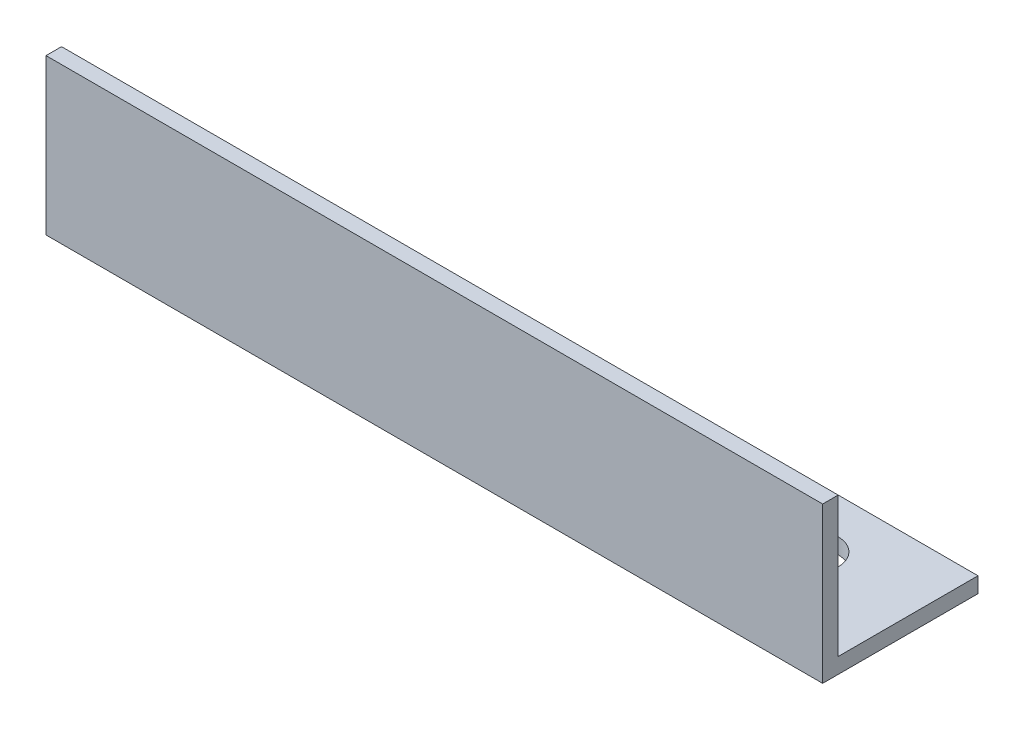
SolidWorks part; units mm, degrees
ref_plane "Спереди" through (0, 0, 0) normal (0, 0, 1) x (1, 0, 0)
ref_plane "Сверху" through (0, 0, 0) normal (0, 1, 0) x (1, 0, 0)
ref_plane "Справа" through (0, 0, 0) normal (1, 0, 0) x (0, 0, -1)
sketch "Эскиз1" plane through (0, 0, 0) normal (1, 0, 0) x (0, 0, -1)
  line L0 (0, 0) -> (0, 30)
  line L1 (0, 0) -> (30, 0)
extrude "Вытянуть-Тонкостенный1" add sketch "Эскиз1" along normal blind 150 thin thin type one direction reverse wall 3
sketch "Эскиз2" plane through (0, 0, 0) normal (0, -1, 0) x (1, 0, 0)
  line L0 (75, -35.357) -> (75, 2.5686) construction
  circle A0 centre (130, -18) radius 5
  circle A1 centre (100, -18) radius 5
  circle A2 centre (50, -18) radius 5
  circle A3 centre (20, -18) radius 5
  dimension "D1" = 2
extrude "Вырез-Вытянуть1" cut sketch "Эскиз2" against normal through all
